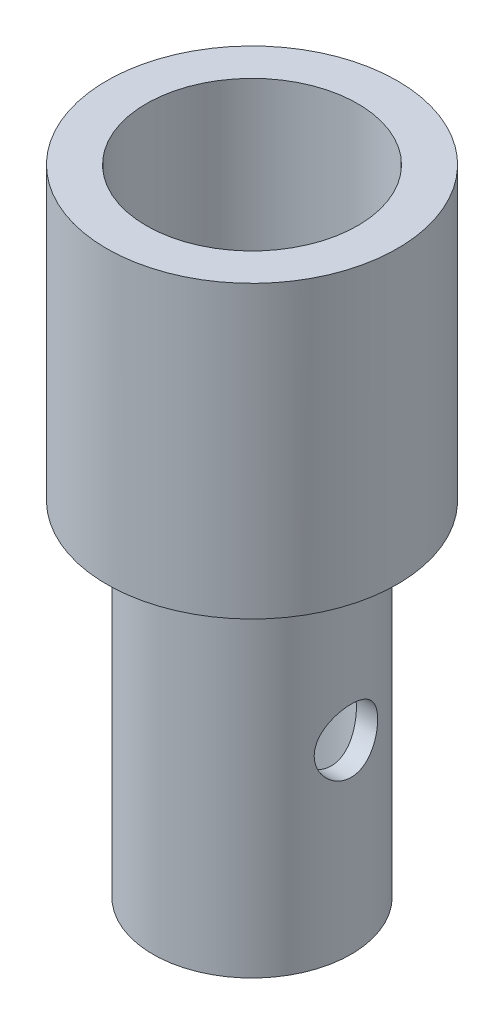
SolidWorks part; units mm, degrees
note: '?' marks a value the reader was unsure of.
ref_plane "Front Plane" through (0, 0, 0) normal (0, 0, 1) x (1, 0, 0)
ref_plane "Top Plane" through (0, 0, 0) normal (0, 1, 0) x (1, 0, 0)
ref_plane "Right Plane" through (0, 0, 0) normal (1, 0, 0) x (0, 0, -1)
sketch "Sketch1" plane through (0, 0, 0) normal (0, 1, 0) x (1, 0, 0)
  circle A0 centre (0, 0) radius 12.7
  circle A1 centre (0, 0) radius 17.4625
  dimension "D1" = 25.4
  dimension "D2" = 4.7625
extrude "spring_chamber" add sketch "Sketch1" along normal blind 28.575 contours A1 A0
sketch "Sketch2" plane through (0, 0, 0) normal (0, -1, 0) x (1, 0, 0)
  circle A0 centre (0, 0) radius 9.525
  circle A1 centre (0, 0) radius 17.4625 construction
  circle A2 centre (0, 0) radius 17.4625
  dimension "D1" = 19.05
extrude "ball_chamber" add sketch "Sketch2" along normal blind 47.625
ref_axis "Axis1" through (0, 28.575, 0) along (0, -1, 0)?
sketch "Sketch3" plane through (0, -47.625, 0) normal (0, -1, 0) x (1, 0, 0)
  circle A0 centre (0, 0) radius 17.4625 construction
  circle A1 centre (0, 0) radius 17.4625
sketch "Sketch5" plane through (0, 0, 0) normal (1, 0, 0) x (0, 0, -1)
  line L0 (12.7, 0) -> (-12.7, 0) construction
  line L1 (-17.4625, -47.625) -> (17.4625, -47.625) construction
  line L2 (-17.4625, -47.625) -> (17.4625, -47.625)
  line L4 (12.7, 0) -> (-12.7, 0)
  circle A0 centre (0, -25.4) radius 3.81
  point P4 (0, 0)
  dimension "D1" = 7.62
  dimension "D2" = 25.4
extrude "ball_hole" cut sketch "Sketch5" along normal through all contours A0
sketch "Sketch8" plane through (0, -47.625, 0) normal (0, -1, 0) x (1, 0, 0)
  circle A0 centre (0, 0) radius 11.9062
  circle A5 centre (0, 0) radius 9.525 construction
  circle A6 centre (0, 0) radius 9.525
  dimension "D1" = 2.3812
extrude "Cut-Extrude2" cut sketch "Sketch8" against normal offset from surface (41.275 mm away) 6.35
mirror "Mirror1" about plane through (0, 0, 0) normal (1, 0, 0) of "ball_hole"
